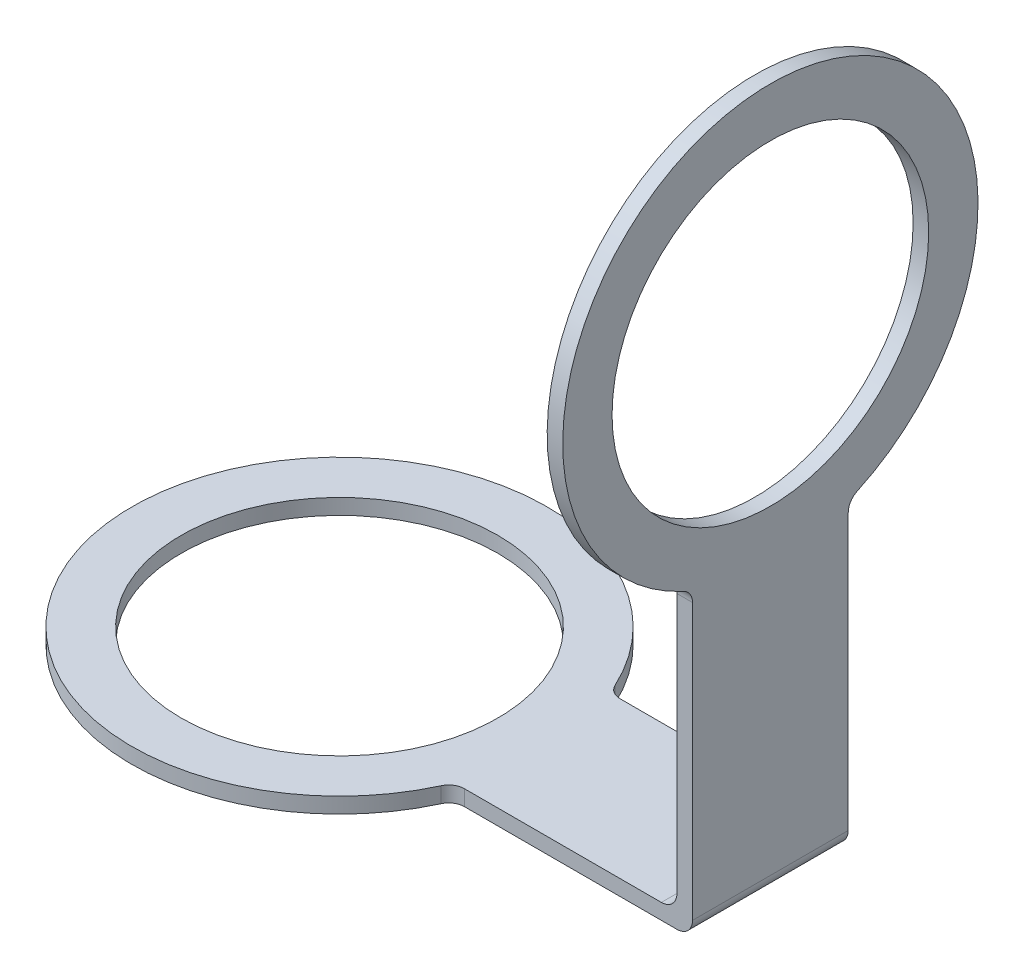
SolidWorks part; units mm, degrees
ref_plane "Front Plane" through (0, 0, 0) normal (0, 0, 1) x (1, 0, 0)
ref_plane "Top Plane" through (0, 0, 0) normal (0, 1, 0) x (1, 0, 0)
ref_plane "Right Plane" through (0, 0, 0) normal (1, 0, 0) x (0, 0, -1)
sketch "Sketch1" plane through (0, 0, 0) normal (0, 1, 0) x (1, 0, 0)
  circle A0 centre (0, 0) radius 40
  circle A1 centre (0, 0) radius 30.5
  dimension "D1" = 80
  dimension "D2" = 61
extrude "Boss-Extrude1" add sketch "Sketch1" along normal blind 3
sketch "Sketch2" plane through (0, 3, 0) normal (0, 1, 0) x (1, 0, 0)
  line L1 (35, 15) -> (83, 15)
  line L2 (35, 15) -> (35, -15)
  line L3 (35, -15) -> (83, -15)
  line L4 (83, 15) -> (83, -15)
  circle A0 centre (0, 0) radius 30.5 construction
  dimension "D1" = 30
  dimension "D2" = 15
  dimension "D3" = 35
  dimension "D4" = 48
extrude "Boss-Extrude2" add sketch "Sketch2" against normal up to surface (3 mm away) up to face at (0, 0, 40)
sketch "Sketch3" plane through (83, 0, 0) normal (1, 0, 0) x (0, 0, -1)
  line L0 (15, 0) -> (15, 3) construction
  line L1 (-15, 0) -> (15, 0)
  line L2 (-15, 0) -> (-15, 58)
  line L4 (15, 0) -> (15, 58)
  arc A0 (15, 58) -> (-15, 58) centre (0, 95.081) ccw
  circle A1 centre (0, 95.081) radius 30.5
  dimension "D1" = 80
  dimension "D2" = 61
  dimension "D3" = 58
extrude "Boss-Extrude3" add sketch "Sketch3" against normal blind 3
fillet "Fillet1" radius 3 4 edges at (37.081, 1.5, 15) (37.081, 1.5, -15) (81.5, 58, 15) (81.5, 58, -15)
fillet "Fillet2" radius 3 2 edges at (80, 3, 0) (83, 0, 0)
